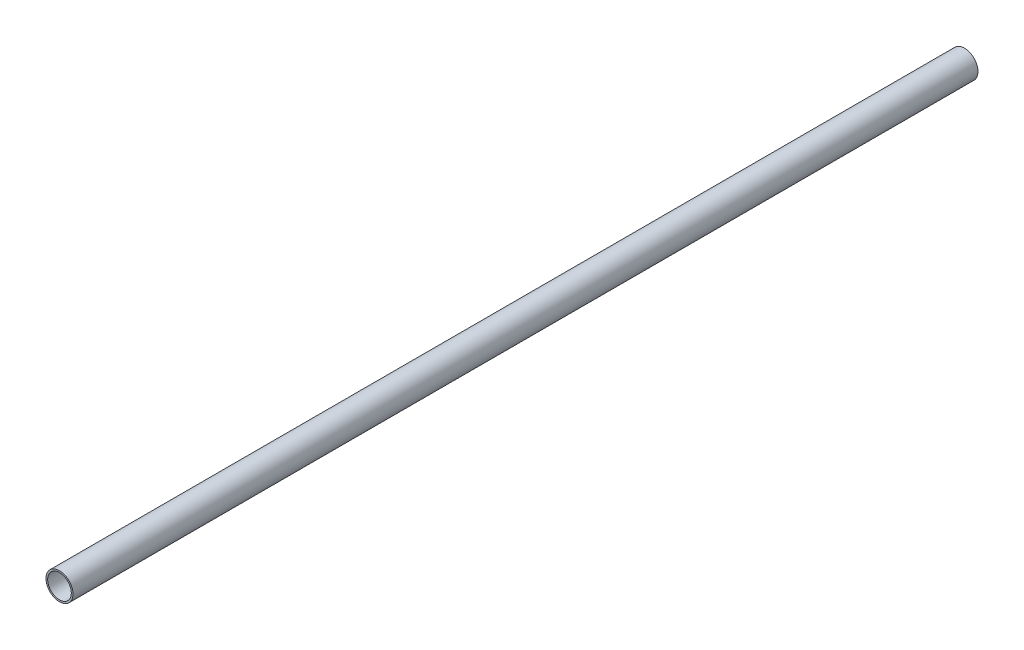
SolidWorks part; units mm, degrees
material "Galvanized Steel"
ref_plane "Front Plane" through (0, 0, 0) normal (0, 0, 1) x (1, 0, 0)
ref_plane "Top Plane" through (0, 0, 0) normal (0, 1, 0) x (1, 0, 0)
ref_plane "Right Plane" through (0, 0, 0) normal (1, 0, 0) x (0, 0, -1)
sketch "Sketch1" plane through (0, 0, 0) normal (0, 0, 1) x (1, 0, 0)
  circle A0 centre (0, 0) radius 11.1125
  circle A1 centre (0, 0) radius 12.7
  dimension "D1" = 25.4
  dimension "D2" = 1.5875
extrude "Boss-Extrude1" add sketch "Sketch1" along normal blind 914.4
sketch "Sketch2" plane through (0, 0, 0) normal (0, 1, 0) x (1, 0, 0)
  line L0 (12.7, -914.4) -> (12.7, 0) construction
  line L1 (-12.7, -914.4) -> (12.7, -914.4)
  line L2 (-12.7, -914.4) -> (-12.7, -850.9)
  line L3 (-12.7, -850.9) -> (12.7, -850.9)
  line L4 (12.7, -914.4) -> (12.7, -850.9)
  dimension "D1" = 63.5
extrude "Cut-Extrude1" cut sketch "Sketch2" against normal blind 19.05 and the other way blind 19.05
